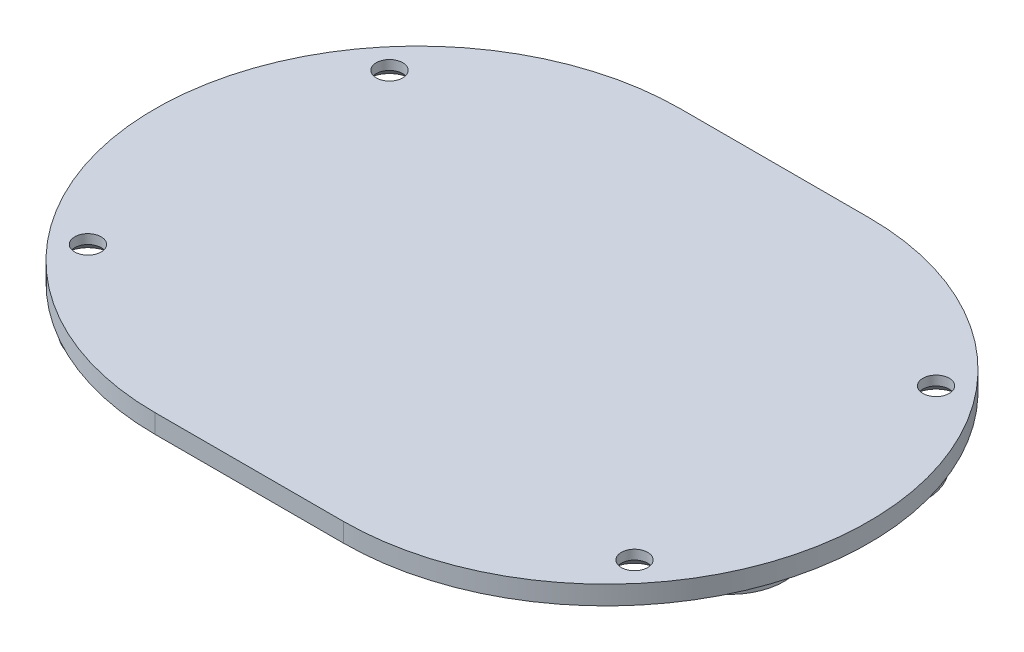
SolidWorks part; units mm, degrees
ref_plane "Front Plane" through (0, 0, 0) normal (0, 0, 1) x (1, 0, 0)
ref_plane "Top Plane" through (0, 0, 0) normal (0, 1, 0) x (1, 0, 0)
ref_plane "Right Plane" through (0, 0, 0) normal (1, 0, 0) x (0, 0, -1)
sketch "Sketch1" plane through (0, 2, 0) normal (0, -1, 0) x (1, 0, 0)
  line L0 (0, -27.9) -> (20, -27.9)
  line L1 (20, 27.9) -> (0, 27.9)
  line L2 (0, -28) -> (20, -28)
  line L3 (20, 28) -> (0, 28)
  line L4 (0, -28) -> (20, -28) construction
  line L5 (20, 28) -> (0, 28) construction
  arc A0 (20, -27.9) -> (20, 27.9) centre (20, 0) ccw
  arc A1 (0, 27.9) -> (0, -27.9) centre (0, 0) ccw
  arc A2 (0, 28) -> (0, -28) centre (0, 0) ccw
  arc A3 (20, -28) -> (20, 28) centre (20, 0) ccw
  arc A4 (0, 28) -> (0, -28) centre (0, 0) ccw construction
  arc A5 (20, -28) -> (20, 28) centre (20, 0) ccw construction
  dimension "D1" = 0
  dimension "D2" = 0.1
extrude "Boss-Extrude1" add sketch "Sketch1" along normal blind 2
hole_wizard "CSK for ST2.2 Cross recessed CTSK head tapping screws1" positions "Sketch2" profile "Sketch3" countersink size "ST2.2" standard "GB"
sketch "Sketch2" plane through (0, 0, 0) normal (0, -1, 0) x (-1, 0, 0)
  line L0 (0, 0) -> (-20, 0) construction
  line L3 (-39, 16) -> (19, 16)
  line L4 (-39, 16) -> (-39, -16)
  line L5 (-39, -16) -> (19, -16)
  line L6 (19, 16) -> (19, -16)
  line L7 (-10, 0) -> (-10, 22.0512) construction
  point P0 (-39, 16)
  point P2 (-39, -16)
  point P4 (19, -16)
  point P6 (19, 16)
  dimension "D1" = 32
  dimension "D2" = 58
sketch "Sketch3" plane through (39, 0, -16) normal (1, 0, 0) x (0, 0, -1)
  line L0 (0, 0) -> (0, 8.3412)
  line L1 (0, 8.3412) -> (1.4, 7.5)
  line L2 (1.4, 7.5) -> (1.4, 1)
  line L3 (1.4, 1) -> (2.4, 0)
  line L5 (2.4, 0) -> (0, 0)
  line L6 (-1.4, 1) -> (-2.4, 0) construction
  line L10 (0, 8.3412) -> (-1.4, 7.5) construction
  line L11 (0, -6.35) -> (0, 107.95) construction
  dimension "Hole Dia." = 2.8
  dimension "Hole Depth" = 7.5
  dimension "Near C'Sink Dia." = 4.8
  dimension "Near C'Sink Angle" = 90
  dimension "Drill Angle" = 118
sketch "Sketch4" plane through (0, 0, 0) normal (0, -1, 0) x (1, 0, 0)
  circle A0 centre (-11, 19.0526) radius 4.25
  circle A1 centre (-11, -19.0526) radius 4.25
  circle A2 centre (40.6732, 7.5244) radius 4.25
  circle A3 centre (40.6732, -7.5244) radius 4.25
  dimension "D1" = 8.5
extrude "Extrude-Thin1" add sketch "Sketch4" along normal blind 0.5 thin thin type one direction wall 1.5
